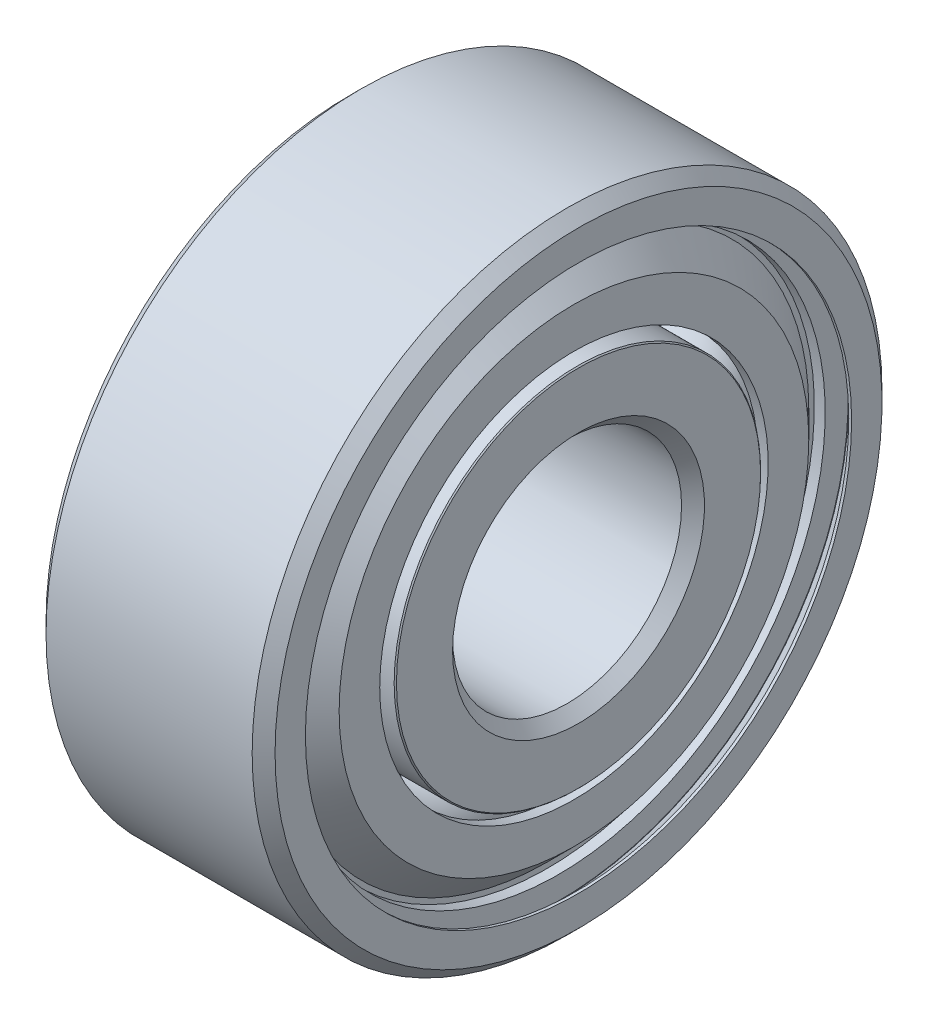
SolidWorks part; units mm, degrees
ref_plane "Front Plane" through (0, 0, 0) normal (0, 0, 1) x (1, 0, 0)
ref_plane "Top Plane" through (0, 0, 0) normal (0, 1, 0) x (1, 0, 0)
ref_plane "Right Plane" through (0, 0, 0) normal (1, 0, 0) x (0, 0, -1)
sketch "Sketch1" plane through (0, 0, 0) normal (0, 0, 1) x (1, 0, 0)
  line L0 (-2, 3.18) -> (-2, 2.2)
  line L1 (-1.8, 2) -> (1.8, 2)
  line L2 (2, 2.2) -> (2, 3.18)
  line L3 (1.98, 3.2) -> (1.0087, 3.2)
  line L4 (-1.98, 3.2) -> (-2, 3.18)
  line L5 (0, 0) -> (0, 26.3443) construction
  line L6 (-2, 2.2) -> (-1.8, 2)
  line L7 (1.8, 2) -> (2, 2.2)
  line L8 (2, 3.18) -> (1.98, 3.2)
  line L9 (0, 0) -> (38.1203, 0) construction
  line L10 (-2, 5.3) -> (-1.8, 5.5)
  line L11 (-1.25, 4.5) -> (-1.0087, 4.5)
  line L12 (-2, 4.77) -> (-2, 5.3)
  line L13 (-1.8, 5.5) -> (1.8, 5.5)
  line L14 (2, 4.77) -> (2, 5.3)
  line L15 (-2, 4.77) -> (-1.95, 4.77)
  line L16 (-1.95, 4.77) -> (-1.65, 5.07)
  line L17 (1.8, 5.5) -> (2, 5.3)
  line L18 (1.0087, 4.5) -> (1.25, 4.5)
  line L19 (-1.0087, 3.2) -> (-1.98, 3.2)
  line L20 (-1.65, 5.07) -> (-1.45, 5.07)
  line L21 (-1.45, 5.07) -> (-1.45, 4.77)
  line L22 (-1.45, 4.77) -> (-1.25, 4.77)
  line L23 (-1.25, 4.77) -> (-1.25, 4.5)
  line L24 (1.25, 4.77) -> (1.25, 4.5)
  line L25 (1.45, 4.77) -> (1.25, 4.77)
  line L26 (1.45, 5.07) -> (1.45, 4.77)
  line L27 (1.65, 5.07) -> (1.45, 5.07)
  line L28 (1.95, 4.77) -> (1.65, 5.07)
  line L29 (2, 4.77) -> (1.95, 4.77)
  line L30 (-1.447, 4.7565) -> (-1.447, 4.5746)
  line L31 (-1.6489, 5.0604) -> (-1.4589, 5.0604)
  line L32 (-1.6489, 5.0604) -> (-1.6489, 4.6604)
  line L33 (-1.6489, 4.6604) -> (-1.4589, 4.6604)
  line L34 (-1.4589, 5.0604) -> (-1.4589, 4.6604)
  line L35 (-1.447, 4.5746) -> (-1.9204, 4.1012)
  line L36 (-1.9204, 4.1012) -> (-1.9204, 3.3925)
  line L37 (-1.9204, 3.3925) -> (-1.7404, 3.3925)
  line L38 (-1.7404, 3.3925) -> (-1.7404, 4.0267)
  line L39 (-1.7404, 4.0267) -> (-1.267, 4.5)
  line L40 (-1.267, 4.5) -> (-1.267, 4.7565)
  line L41 (-1.267, 4.7565) -> (-1.447, 4.7565)
  line L42 (1.6489, 5.0604) -> (1.4589, 5.0604)
  line L43 (1.6489, 5.0604) -> (1.6489, 4.6604)
  line L44 (1.6489, 4.6604) -> (1.4589, 4.6604)
  line L45 (1.4589, 5.0604) -> (1.4589, 4.6604)
  line L46 (1.267, 4.7565) -> (1.447, 4.7565)
  line L47 (1.447, 4.7565) -> (1.447, 4.5746)
  line L48 (1.267, 4.5) -> (1.267, 4.7565)
  line L49 (1.7404, 4.0267) -> (1.267, 4.5)
  line L50 (1.447, 4.5746) -> (1.9204, 4.1012)
  line L51 (1.9204, 3.3925) -> (1.7404, 3.3925)
  line L52 (1.7404, 3.3925) -> (1.7404, 4.0267)
  line L53 (1.9204, 4.1012) -> (1.9204, 3.3925)
  line L54 (0, 5) -> (0, 2.7)
  arc A0 (-1.0087, 3.2) -> (1.0087, 3.2) centre (0, 3.85) ccw
  arc A1 (1.0087, 4.5) -> (-1.0087, 4.5) centre (0, 3.85) ccw
  circle A2 centre (0, 3.85) radius 1.15
  point P0 (-2, 3.2)
  point P1 (-2, 2)
  point P3 (2, 2)
  point P4 (2, 3.2)
  point P18 (-2, 4.5)
  point P19 (2, 5.5)
  point P20 (-2, 5.5)
  point P21 (2, 4.5)
  dimension "D11" = 1.2
  dimension "D25" = 2.3
  dimension "D1" = 2
  dimension "D2" = 4
  dimension "D7" = 3.2
  dimension "D8" = 0.05
  dimension "D9" = 5.5
  dimension "D12" = 45
  dimension "D10" = 0.65
  dimension "D14" = 0.2
  dimension "D15" = 0.2
  dimension "D17" = 4.77
  dimension "D18" = 0.3
  dimension "D19" = 4.5
  dimension "D20" = 0.19
  dimension "D21" = 0.4
  dimension "D22" = 0.18
  dimension "D23" = 0.18
  dimension "D24" = 45
revolve "Revolve1" add sketch "Sketch1" angle 360 about L9 region at (0, 2.5316, 0) region at (0, 5.1431, 0)
revolve "Revolve2" add sketch "Sketch1<3>" angle 360 about L9 region at (-1.357, 4.7414, 0) region at (1.357, 4.7414, 0)
sketch "Sketch1<3>" plane through (0, 0, 0) normal (0, 0, 1) x (1, 0, 0) same geometry as "Sketch1"
revolve "Revolve3" add sketch "Sketch1<4>" angle 360 about L9 region at (1.5539, 4.8604, 0)
sketch "Sketch1<4>" plane through (0, 0, 0) normal (0, 0, 1) x (1, 0, 0) same geometry as "Sketch1"
revolve "Revolve4" add sketch "Sketch1<5>" angle 360 about L54 region at (0.4881, 3.85, 0)
sketch "Sketch1<5>" plane through (0, 0, 0) normal (0, 0, 1) x (1, 0, 0) same geometry as "Sketch1"
pattern_circular "CirPattern2" count 8 over 360 about axis through (0, 0, 0) along (-1, 0, 0) of bodies 111
